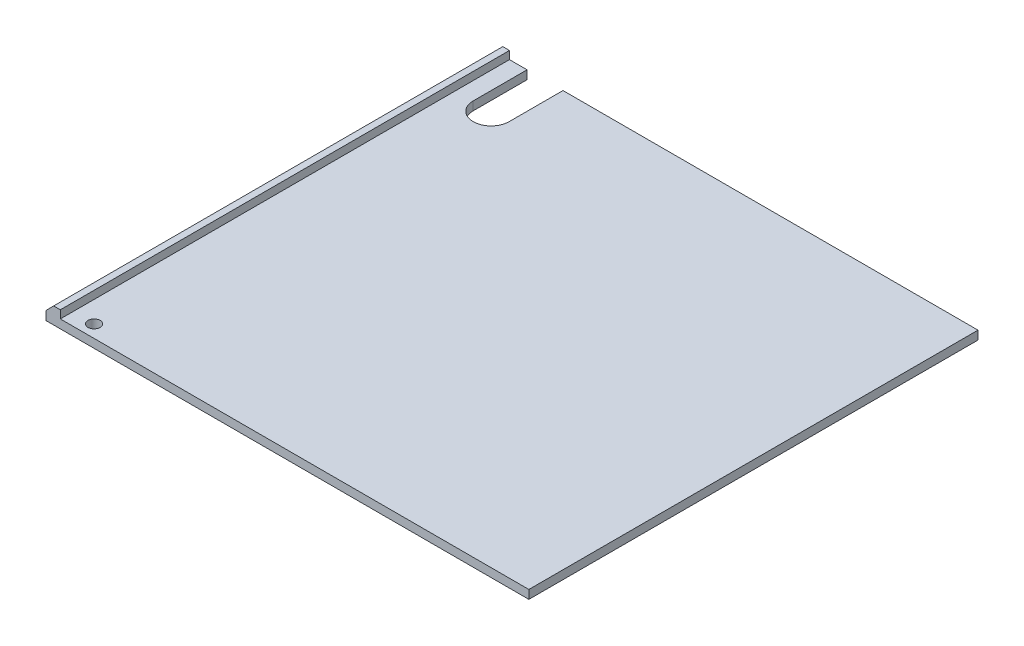
SolidWorks part; units mm, degrees
note: '?' marks a value the reader was unsure of.
material "ABS"
ref_plane "Front Plane" through (0, 0, 0) normal (0, 0, 1) x (1, 0, 0)
ref_plane "Top Plane" through (0, 0, 0) normal (0, 1, 0) x (1, 0, 0)
ref_plane "Right Plane" through (0, 0, 0) normal (1, 0, 0) x (0, 0, -1)
ref_axis "Axis1" through (0, 0, 55) along (0, 0, -1)?
sketch "Sketch1" plane through (0, 0, 0) normal (0, 1, 0) x (1, 0, 0)
  line L1 (-64.25, 62.5) -> (64.25, 62.5)
  line L2 (-64.25, 62.5) -> (-64.25, -62.5)
  line L3 (-64.25, -62.5) -> (64.25, -62.5)
  line L4 (64.25, 62.5) -> (64.25, -62.5)
  line L5 (-64.25, 62.5) -> (64.25, -62.5) construction
  line L6 (-64.25, -62.5) -> (64.25, 62.5) construction
  point P0 (0, 0)
  dimension "D1" = 128.5
  dimension "D2" = 125
extrude "Boss-Extrude1" add sketch "Sketch1" along normal blind 2.4
sketch "4040-extrusion" plane through (0, 0, 62.5) normal (0, 0, 1) x (1, 0, 0)
  line L0 (-64.25, 0) -> (-64.25, 9.5) construction
  line L1 (-64.25, 9.5) -> (-64.25, 4.3) construction
  line L2 (-64.25, 4.3) -> (-66.05, 2.5) construction
  line L3 (-66.05, 2.5) -> (-66.05, 4.71) construction
  line L4 (-66.05, 4.71) -> (-68.05, 4.71) construction
  line L5 (-68.05, 4.71) -> (-70.2381, 2.5) construction
  line L6 (-70.2381, 2.5) -> (-70.2381, 0) construction
  dimension "D1" = 9.5
  dimension "D2" = 5.2
  dimension "D3" = 7
  dimension "D4" = 1.8
  dimension "D5" = 2.21
  dimension "D6" = 2
  dimension "D7" = 3.11
sketch "Sketch3" plane through (0, 0, 62.5) normal (0, 0, 1) x (1, 0, 0)
  line L0 (-64.25, 2.4) -> (-66.05, 2.4)
  line L1 (-66.05, 2.4) -> (-66.05, 4.71) construction
  line L2 (-66.05, 4.71) -> (-68.05, 4.71) construction
  line L3 (-68.05, 4.71) -> (-70.2381, 2.5) construction
  line L4 (-70.2381, 2.5) -> (-70.2381, 0) construction
  line L5 (-70.2381, 0) -> (-70.1381, 0) construction
  line L6 (-64.25, 0) -> (-64.25, 2.4)
  line L7 (-66.15, 2.4) -> (-66.15, 4.61)
  line L8 (-66.15, 4.61) -> (-68.0083, 4.61)
  line L9 (-68.0083, 4.61) -> (-70.1381, 2.4589)
  line L10 (-70.1381, 2.4589) -> (-70.1381, 0)
  line L11 (-66.15, 2.4) -> (-66.05, 2.4)
  line L12 (-70.1381, 0) -> (-64.25, 0)
  dimension "D1" = 0.1
extrude "Boss-Extrude2" add sketch "Sketch3" against normal up to surface (125 mm away) up to face at (0, 1.2, -62.5)
sketch "Sketch5" plane through (0, 2.4, 0) normal (0, 1, 0) x (1, 0, 0)
  line L0 (-56.25, 62.5) -> (-56.25, 47.5) construction
  line L1 (64.25, 62.5) -> (-66.15, 62.5) construction
  line L2 (-51.25, 62.5) -> (-51.25, 47.5)
  line L3 (-61.25, 62.5) -> (-61.25, 47.5)
  line L5 (-61.25, 62.5) -> (-51.25, 62.5)
  line L6 (-66.15, 62.5) -> (-66.15, -62.5) construction
  arc A0 (-51.25, 62.5) -> (-61.25, 62.5) centre (-56.25, 62.5) ccw
  arc A1 (-61.25, 47.5) -> (-51.25, 47.5) centre (-56.25, 47.5) ccw
  point P4 (-56.25, 55)
  dimension "D1" = 5
  dimension "D3" = 15
  dimension "D2" = 9.9
extrude "Cut-Extrude2" cut sketch "Sketch5" against normal through all
sketch "Sketch6" plane through (0, 2.4, 0) normal (0, 1, 0) x (1, 0, 0)
  line L0 (-60.25, -59) -> (-66.15, -59) construction
  line L1 (-66.15, -62.5) -> (64.25, -62.5) construction
  line L3 (-63.75, -62.5) -> (-56.75, -62.5) construction
  line L4 (-63.75, -62.5) -> (-63.75, -55.5) construction
  line L5 (-63.75, -55.5) -> (-56.75, -55.5) construction
  line L6 (-56.75, -62.5) -> (-56.75, -55.5) construction
  line L7 (-63.75, -62.5) -> (-56.75, -55.5) construction
  line L8 (-63.75, -55.5) -> (-56.75, -62.5) construction
  line L9 (-66.15, 62.5) -> (-66.15, -62.5) construction
  circle A0 centre (-60.25, -59) radius 1.7
  point P8 (-60.25, -59)
  dimension "D3" = 3.4
  dimension "D1" = 5.9
  dimension "D2" = 7
extrude "Cut-Extrude3" cut sketch "Sketch6" against normal through all
equation "\"D1@Sketch1\"=125mm+3.5mm"
equation "\"D2@Sketch5\"=5+2+2.3+.1+.5"
